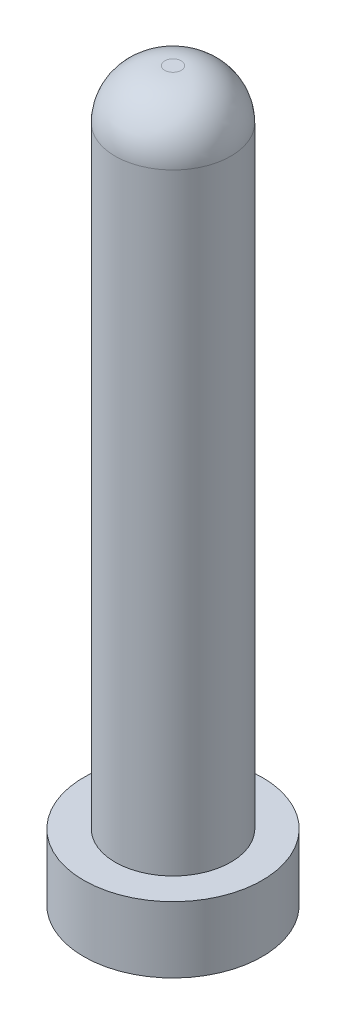
SolidWorks part; units mm, degrees
ref_plane "Front Plane" through (0, 0, 0) normal (0, 0, 1) x (1, 0, 0)
ref_plane "Top Plane" through (0, 0, 0) normal (0, 1, 0) x (1, 0, 0)
ref_plane "Right Plane" through (0, 0, 0) normal (1, 0, 0) x (0, 0, -1)
sketch "Sketch1" plane through (0, 0, 0) normal (0, 1, 0) x (1, 0, 0)
  line L1 (-2.8, -2.7) -> (2.8, -2.7) construction
  line L2 (-2.8, -2.7) -> (-2.8, 2.7) construction
  line L3 (-2.8, 2.7) -> (2.8, 2.7) construction
  line L4 (2.8, -2.7) -> (2.8, 2.7) construction
  line L5 (-2.8, -2.7) -> (2.8, 2.7) construction
  line L6 (-2.8, 2.7) -> (2.8, -2.7) construction
  circle A0 centre (0, 0) radius 2.7
  point P0 (0, 0)
  dimension "D1" = 5.6
  dimension "D2" = 5.4
extrude "Boss-Extrude1" add sketch "Sketch1" along normal blind 2
sketch "Sketch2" plane through (0, 2, 0) normal (0, 1, 0) x (1, 0, 0)
  circle A0 centre (0, 0) radius 1.75
  dimension "D1" = 3.5
sketch "Sketch3" plane through (0, 0, 0) normal (0, -1, 0) x (1, 0, 0)
  circle A0 centre (0, 0) radius 1.2
  circle A1 centre (0, 0) radius 0.95
  point P0 (0, 0)
  dimension "D1" = 2.4
  dimension "D2" = 1.9
extrude "Cut-Extrude2" cut sketch "Sketch3" against normal blind 9.5 contours A1
sketch "Sketch7" plane through (0, 0, 0) normal (0, -1, 0) x (1, 0, 0)
  circle A0 centre (0, 0) radius 1.2
  dimension "D1" = 2.4
extrude "Cut-Extrude4" cut sketch "Sketch7" against normal blind 2.8
extrude "Boss-Extrude2" add sketch "Sketch2" along normal blind 20
fillet "Fillet2" radius 1.5 1 edges at (0, 22, 1.75)
sketch "Sketch8" plane through (0, 0, 0) normal (0, -1, 0) x (1, 0, 0)
  circle A0 centre (0, 0) radius 0.95
  dimension "D1" = 1.9
extrude "Cut-Extrude5" cut sketch "Sketch8" against normal blind 9.5
